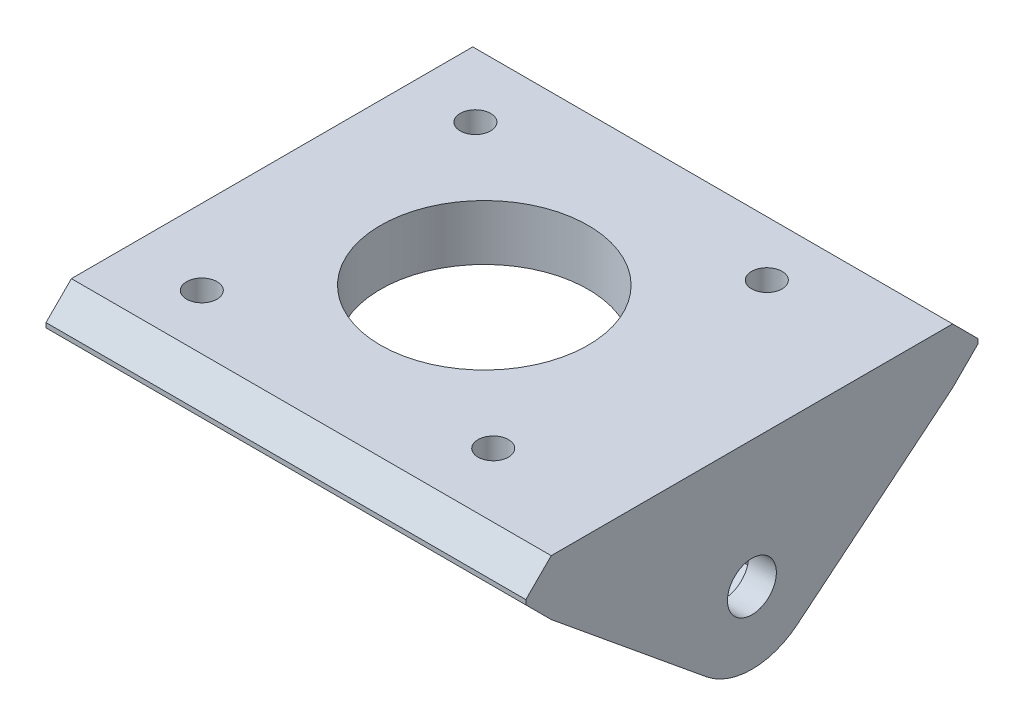
SolidWorks part; units mm, degrees
ref_plane "Front Plane" through (0, 0, 0) normal (0, 0, 1) x (1, 0, 0)
ref_plane "Top Plane" through (0, 0, 0) normal (0, 1, 0) x (1, 0, 0)
ref_plane "Right Plane" through (0, 0, 0) normal (1, 0, 0) x (0, 0, -1)
sketch "Sketch1" plane through (0, 0, 0) normal (0, 1, 0) x (1, 0, 0)
  line L1 (-23, -24.5) -> (23, -24.5)
  line L2 (-23, -24.5) -> (-23, 24.5)
  line L3 (-23, 24.5) -> (23, 24.5)
  line L4 (23, -24.5) -> (23, 24.5)
  line L5 (-23, -24.5) -> (23, 24.5) construction
  line L6 (-23, 24.5) -> (23, -24.5) construction
  circle A0 centre (0, 0) radius 11.25
  circle A1 centre (14.8249, 15.7917) radius 1.65
  circle A2 centre (15.7917, -14.8249) radius 1.65
  circle A3 centre (-14.8249, -15.7917) radius 1.65
  circle A4 centre (-15.7917, 14.8249) radius 1.65
  point P0 (0, 0)
  point P19 (0, 0)
  dimension "D2" = 22.5
  dimension "D3" = 21.66
  dimension "D4" = 3.3
  dimension "D1" = 46
  dimension "D6" = 49
  dimension "D5" = 4
extrude "Boss-Extrude1" add sketch "Sketch1" along normal blind 6
chamfer "Chamfer1" distance 2.75 angle 45 4 edges at (0, 0, -24.5) (0, 6, -24.5) (0, 6, 24.5) (0, 0, 24.5)
sketch "Sketch2" plane through (23, 0, 0) normal (1, 0, 0) x (0, 0, -1)
  line L1 (-21.75, 6) -> (21.75, 6)
  line L2 (-21.75, 6) -> (-21.75, 0)
  line L4 (21.75, 6) -> (21.75, 0)
  line L5 (0, -12.681) -> (4.25, -10.2272)
  line L6 (4.25, -10.2272) -> (4.25, -5.3198)
  line L7 (4.25, -5.3198) -> (0, -2.866)
  line L8 (0, -2.866) -> (-4.25, -5.3198)
  line L9 (-4.25, -5.3198) -> (-4.25, -10.2272)
  line L10 (-4.25, -10.2272) -> (0, -12.681)
  line L11 (21.75, 0) -> (4.9272, -13.786)
  line L12 (-21.75, 0) -> (-4.9272, -13.786)
  circle A0 centre (0, -7.7735) radius 4.25 construction
  arc A1 (-4.9272, -13.786) -> (4.9272, -13.786) centre (0, -7.7735) ccw
  dimension "D1" = 8.5
extrude "Boss-Extrude2" add sketch "Sketch2" along normal blind 3
sketch "Sketch3" plane through (26, 0, 0) normal (1, 0, 0) x (0, 0, -1)
  line L0 (-21.75, 6) -> (21.75, 6)
  line L1 (21.75, 6) -> (21.75, 0)
  line L2 (21.75, 0) -> (4.9272, -13.786)
  line L3 (-21.75, 0) -> (-4.9272, -13.786)
  arc A0 (-4.9272, -13.786) -> (4.9272, -13.786) centre (0, -7.7735) ccw
  circle A1 centre (0, -7.7735) radius 2.65
  line M6 (-21.75, 6) -> (-21.75, 0)
  line M7 (-21.75, 0) -> (-4.9272, -13.786)
  arc M8 (-4.9272, -13.786) -> (4.9272, -13.786) centre (0, -7.7735) ccw
  line M9 (4.9272, -13.786) -> (21.75, 0)
  line M10 (21.75, 0) -> (21.75, 6)
  line M11 (21.75, 6) -> (-21.75, 6)
  line M12 (4.25, -10.2272) -> (0, -12.681)
  line M13 (0, -12.681) -> (-4.25, -10.2272)
  line M14 (-4.25, -10.2272) -> (-4.25, -5.3198)
  line M15 (-4.25, -5.3198) -> (0, -2.866)
  line M16 (0, -2.866) -> (4.25, -5.3198)
  line M17 (4.25, -5.3198) -> (4.25, -10.2272)
  dimension "D1" = 5.3
extrude "Boss-Extrude3" add sketch "Sketch3" along normal blind 3 contours M11 M6 M7 M8 M9 M10 M17 M12 M13 M14 M15 M16 | A1 M12 M17 M16 M15 M14 M13 region at (26, -1.5651, 0) region at (26, -11.3417, -2.0601)
sketch "Sketch4" plane through (23, 0, 0) normal (1, 0, 0) x (0, 0, -1)
  line L4 (-21.75, 0) -> (-21.75, 6)
  line L5 (-21.75, 6) -> (-24.5, 3.25)
  line L6 (-24.5, 3.25) -> (-24.5, 2.75)
  line L7 (-24.5, 2.75) -> (-21.75, 0)
  line L8 (-21.75, 0) -> (-21.75, 6)
  line L9 (-21.75, 6) -> (-24.5, 3.25)
  line L10 (-24.5, 3.25) -> (-24.5, 2.75)
  line L11 (-24.5, 2.75) -> (-21.75, 0)
  line L12 (21.75, 6) -> (21.75, 0)
  line L13 (21.75, 0) -> (24.5, 2.75)
  line L14 (24.5, 2.75) -> (24.5, 3.25)
  line L15 (24.5, 3.25) -> (21.75, 6)
  line L16 (21.75, 6) -> (21.75, 0)
  line L17 (21.75, 0) -> (24.5, 2.75)
  line L18 (24.5, 2.75) -> (24.5, 3.25)
  line L19 (24.5, 3.25) -> (21.75, 6)
  dimension "D1" = 0
  dimension "D2" = 0
extrude "Boss-Extrude4" add sketch "Sketch4" along normal up to surface (6 mm away) up to face at (29, -2.8888, 0)
fillet "Fillet1" radius 2 2 edges at (0, 0, 21.75) (0, 0, -21.75) tangent propagation no
